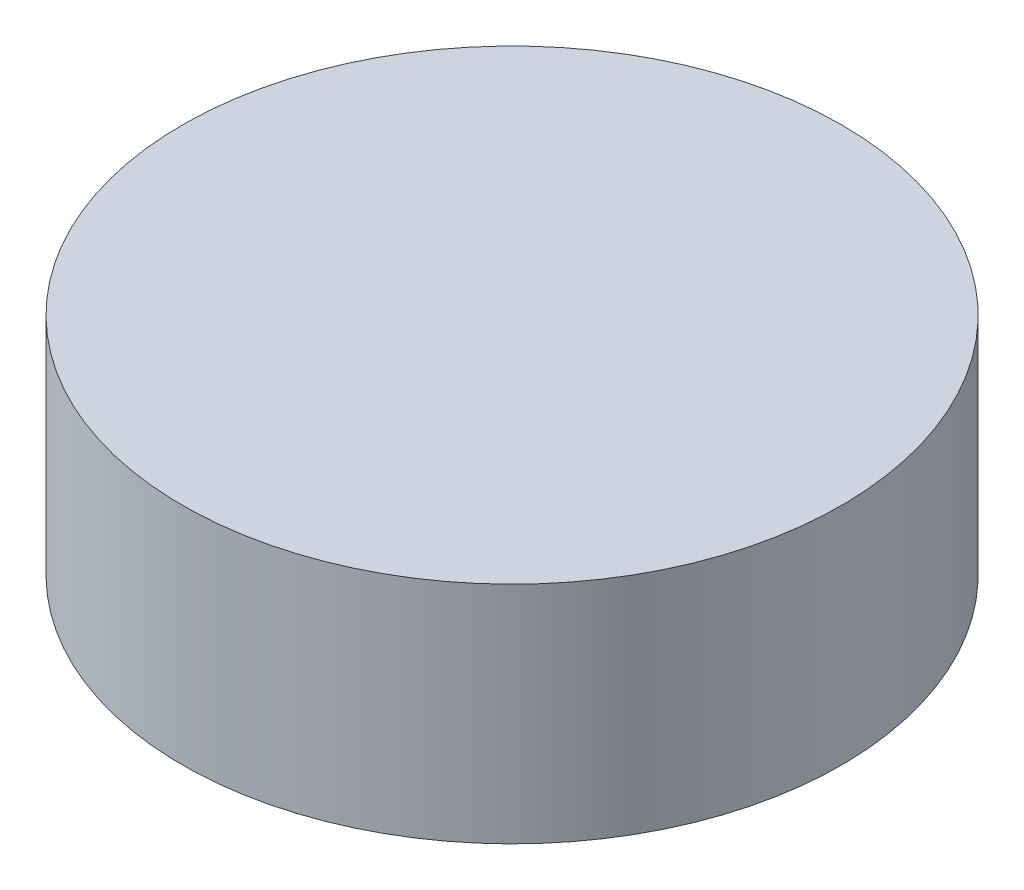
SolidWorks part; units mm, degrees
ref_plane "Front Plane" through (0, 0, 0) normal (0, 0, 1) x (1, 0, 0)
ref_plane "Top Plane" through (0, 0, 0) normal (0, 1, 0) x (1, 0, 0)
ref_plane "Right Plane" through (0, 0, 0) normal (1, 0, 0) x (0, 0, -1)
sketch "Sketch3" plane through (0, 0, 0) normal (0, 1, 0) x (1, 0, 0)
  circle A0 centre (0, 0) radius 19.05
  dimension "D1" = 38.1
extrude "Boss-Extrude1" add sketch "Sketch3" along normal blind 13
sketch "Sketch6" plane through (0, 0, 0) normal (0, -1, 0) x (1, 0, 0)
  circle A0 centre (0, 0) radius 10.127
  dimension "D1" = 20.254
extrude "Cut-Extrude2" cut sketch "Sketch6" against normal blind 8
